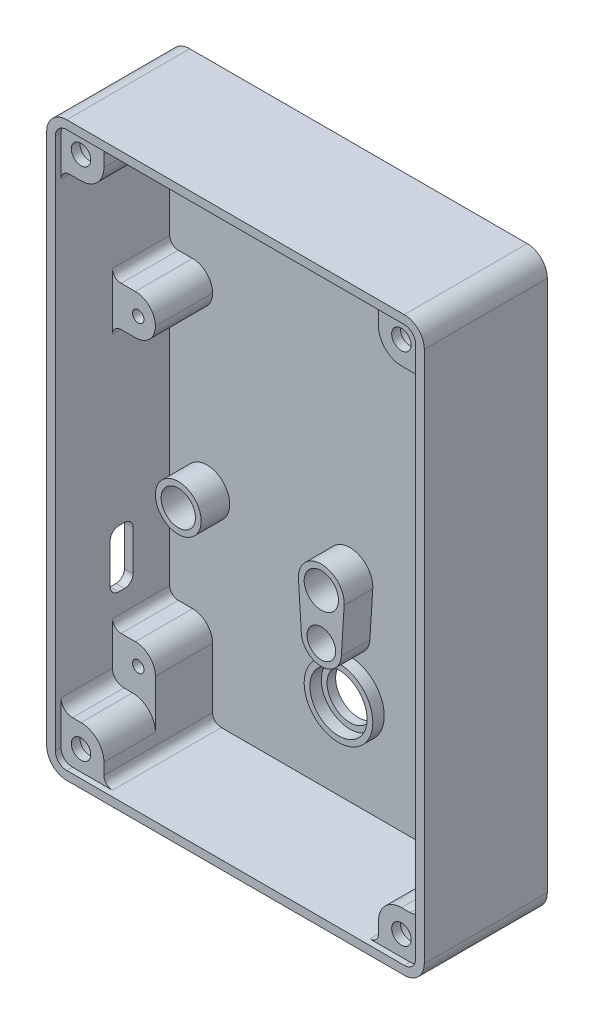
SolidWorks part; units mm, degrees
material "ABS"
ref_plane "Спереди" through (0, 0, 0) normal (0, 0, 1) x (1, 0, 0)
ref_plane "Сверху" through (0, 0, 0) normal (0, 1, 0) x (1, 0, 0)
ref_plane "Справа" through (0, 0, 0) normal (1, 0, 0) x (0, 0, -1)
sketch "Эскиз1" plane through (0, 0, 0) normal (0, 0, 1) x (1, 0, 0)
  line L1 (-33, -50) -> (33, -50)
  line L2 (-33, -50) -> (-33, 50)
  line L3 (-33, 50) -> (33, 50)
  line L4 (33, -50) -> (33, 50)
  line L5 (-33, -50) -> (33, 50) construction
  line L6 (-33, 50) -> (33, -50) construction
  line L7 (-31.5, -48.5) -> (31.5, -48.5)
  line L8 (-31.5, -48.5) -> (-31.5, 48.5)
  line L9 (-31.5, 48.5) -> (31.5, 48.5)
  line L10 (31.5, -48.5) -> (31.5, 48.5)
  line L11 (-31.5, -48.5) -> (31.5, 48.5) construction
  line L12 (-31.5, 48.5) -> (31.5, -48.5) construction
  point P0 (0, 0)
  point P6 (0, 0)
  dimension "D1" = 66
  dimension "D2" = 100
  dimension "D3" = 1.5
  dimension "D4" = 1.5
extrude "Бобышка-Вытянуть1" add sketch "Эскиз1" along normal blind 20
sketch "Эскиз3" plane through (0, 0, 0) normal (0, 0, -1) x (-1, 0, 0)
  line L1 (-33, 50) -> (33, 50)
  line L2 (-33, 50) -> (-33, -50)
  line L3 (-33, -50) -> (33, -50)
  line L4 (33, 50) -> (33, -50)
extrude "Бобышка-Вытянуть2" add sketch "Эскиз3" along normal blind 1.5
sketch "Эскиз4" plane through (0, 0, 0) normal (0, 0, 1) x (1, 0, 0)
  line L0 (-31.5, 48.5) -> (-31.5, -48.5) construction
  line L1 (-31.5, 20) -> (-24, 20)
  line L2 (-31.5, 20) -> (-31.5, 13)
  line L3 (-31.5, 13) -> (-24, 13)
  line L4 (-24, 20) -> (-24, 13)
  line L5 (31.5, -48.5) -> (31.5, 48.5) construction
  line L6 (31.5, 20) -> (24, 20)
  line L7 (31.5, 20) -> (31.5, 13)
  line L8 (31.5, 13) -> (24, 13)
  line L9 (24, 20) -> (24, 13)
  line L10 (-31.5, -48.5) -> (31.5, -48.5) construction
  line L11 (-31.5, -41) -> (-24, -41)
  line L12 (-31.5, -41) -> (-31.5, -33)
  line L13 (-31.5, -33) -> (-24, -33)
  line L14 (-24, -41) -> (-24, -33)
  line L15 (31.5, -41) -> (24, -41)
  line L16 (31.5, -41) -> (31.5, -33)
  line L17 (31.5, -33) -> (24, -33)
  line L18 (24, -41) -> (24, -33)
  line L19 (31.5, -48.5) -> (31.5, 48.5) construction
  dimension "D1" = 7.5
  dimension "D2" = 8
  dimension "D3" = 7
  dimension "D4" = 46
  dimension "D5" = 7.5
extrude "Бобышка-Вытянуть3" add sketch "Эскиз4" along normal blind 10
sketch "Эскиз5" plane through (0, 0, 10) normal (0, 0, 1) x (1, 0, 0)
  line L1 (-24, -41) -> (-24, -33) construction
  line L2 (-24, 13) -> (-24, 20) construction
  circle A0 centre (-27, 16.5) radius 1
  circle A1 centre (27, 16.5) radius 1
  circle A2 centre (-27, -36.5) radius 1
  circle A3 centre (27, -36.5) radius 1
  point P10 (-24, 16.5)
  point P13 (-27, -36.5)
  dimension "D5" = 2
  dimension "D6" = 53
  dimension "D1" = 54
  dimension "D2" = 3
sketch "Эскиз8" plane through (0, 0, 0) normal (0, 0, 1) x (1, 0, 0)
  line L0 (-24, -41) -> (-24, -33) construction
  line L1 (-31.5, 48.5) -> (-24, 48.5)
  line L2 (-31.5, 48.5) -> (-31.5, 41)
  line L3 (-31.5, 41) -> (-24, 41)
  line L4 (-24, 48.5) -> (-24, 41)
  line L5 (31.5, 48.5) -> (24, 48.5)
  line L6 (31.5, 48.5) -> (31.5, 41)
  line L7 (31.5, 41) -> (24, 41)
  line L8 (24, 48.5) -> (24, 41)
  line L9 (31.5, -48.5) -> (24, -48.5)
  line L10 (31.5, -48.5) -> (31.5, -41)
  line L11 (31.5, -41) -> (24, -41)
  line L12 (24, -48.5) -> (24, -41)
  line L13 (-31.5, -48.5) -> (-24, -48.5)
  line L14 (-31.5, -48.5) -> (-31.5, -41)
  line L15 (-31.5, -41) -> (-24, -41)
  line L16 (-24, -48.5) -> (-24, -41)
  line L18 (24, -33) -> (24, -41) construction
  line L19 (-24, 20) -> (-31.5, 20) construction
  line L21 (-31.5, -41) -> (-24, -41) construction
extrude "Бобышка-Вытянуть4" add sketch "Эскиз8" along normal blind 19
fillet "Скругление1" radius 1.5 12 edges at (-31.5, -33, 5) (-24, -48.5, 9.5) (24, -48.5, 9.5) (31.5, -33, 5) (31.5, 13, 5) (31.5, 20, 5) (-31.5, 13, 5) (-31.5, 20, 5) (-31.5, 41, 9.5) (-24, 48.5, 9.5) (31.5, 41, 9.5) (24, 48.5, 9.5)
fillet "Скругление3" radius 2 6 edges at (-31.5, -48.5, 19.5) (-31.5, -41, 14.5) (31.5, -48.5, 19.5) (31.5, -41, 14.5) (-31.5, 48.5, 19.5) (31.5, 48.5, 19.5)
fillet "Скругление4" radius 3.5 4 edges at (-33, -50, 9.25) (33, -50, 9.25) (33, 50, 9.25) (-33, 50, 9.25)
sketch "Эскиз9" plane through (0, 0, 0) normal (0, 0, 1) x (1, 0, 0)
  circle A0 centre (-25, -14) radius 3
  circle A1 centre (25, -14) radius 3
  circle A2 centre (0, -22) radius 2.5
  circle A3 centre (0, -14) radius 3
  circle A4 centre (0, -32.5) radius 4
  dimension "D1" = 6
  dimension "D6" = 8
  dimension "D8" = 5
  dimension "D2" = 8
  dimension "D3" = 10.5
  dimension "D4" = 25
  dimension "D5" = 25
  dimension "D7" = 4
extrude "Вырез-Вытянуть1" cut sketch "Эскиз9" against normal through all
sketch "Эскиз10" plane through (0, 0, 0) normal (0, 0, 1) x (1, 0, 0)
  line L0 (3.9922, -14.25) -> (3.4932, -22.2188)
  line L1 (-3.9922, -14.25) -> (-3.4932, -22.2188)
  circle A0 centre (-25, -14) radius 3
  circle A1 centre (0, -22) radius 2.5 construction
  circle A2 centre (0, -14) radius 3
  circle A3 centre (25, -14) radius 3
  circle A4 centre (0, -22) radius 2.5
  circle A5 centre (-25, -14) radius 3 construction
  circle A6 centre (0, -14) radius 4
  circle A7 centre (25, -14) radius 4
  circle A9 centre (-25, -14) radius 4
  arc A12 (-3.4932, -22.2188) -> (3.4932, -22.2188) centre (0, -22) ccw
  circle M1 centre (-25, -14) radius 3
  circle M2 centre (0, -14) radius 3
  circle M3 centre (0, -22) radius 2.5
  circle M4 centre (25, -14) radius 3
  dimension "D1" = 1
  dimension "D2" = 1
extrude "Бобышка-Вытянуть5" add sketch "Эскиз10" along normal blind 5 contours L1 A12 L0 A6 M3 | A6 M2 | A7 M4 | A9 M1 region at (3.605, -18.2258, 0) region at (0, -17.8869, 0) region at (21.1131, -14, 0) region at (-28.8869, -14, 0)
sketch "Эскиз11" plane through (0, 0, -1.5) normal (0, 0, -1) x (-1, 0, 0)
  line L0 (29.5, 50) -> (-29.5, 50) construction
  line L1 (33, -46.5) -> (33, 46.5) construction
  line L2 (-29.5, -50) -> (29.5, -50) construction
  line L3 (-33, 46.5) -> (-33, -46.5) construction
  circle A0 centre (-28, 45) radius 3
  circle A1 centre (28, 45) radius 3
  circle A2 centre (28, -45) radius 3
  circle A3 centre (-28, -45) radius 3
  dimension "D2" = 6
  dimension "D1" = 5
  dimension "D3" = 5
  dimension "D4" = 5
  dimension "D5" = 5
extrude "Вырез-Вытянуть2" cut sketch "Эскиз11" against normal blind 19
sketch "Эскиз12" plane through (0, 0, 17.5) normal (0, 0, -1) x (-1, 0, 0)
  point P0 (-28, 45)
  point P1 (28, 45)
  point P3 (28, -45)
  point P5 (-28, -45)
hole_wizard "Отверстие с зазором M31" positions "Эскиз13" profile "Эскиз14" hole size "M3" standard "DIN" end condition through all
sketch "Эскиз13" plane through (0, 0, 17.5) normal (0, 0, -1) x (-1, 0, 0)
  point P0 (-28, 45)
  point P3 (28, 45)
  point P6 (28, -45)
  point P9 (-28, -45)
sketch "Эскиз14" plane through (28, 45, 17.5) normal (1, 0, 0) x (0, 1, 0)
  line L0 (0, 0) -> (0, 2.5)
  line L1 (0, 2.5) -> (1.7, 2.5)
  line L2 (1.7, 2.5) -> (1.7, 0)
  line L5 (1.7, 0) -> (0, 0)
  line L11 (0, -6.35) -> (0, 107.95) construction
  dimension "Диаметр сквозного отверстия" = 3.4
  dimension "Глубина сквозного отверстия" = 2.5
extrude "Вырез-Вытянуть4" cut sketch "Эскиз5" against normal blind 4
sketch "Эскиз15" plane through (-31.5, 0, 0) normal (-1, 0, 0) x (0, 0, 1)
  line L1 (6.4, -28) -> (10.4, -28)
  line L2 (6.4, -28) -> (6.4, -18)
  line L3 (6.4, -18) -> (10.4, -18)
  line L4 (10.4, -28) -> (10.4, -18)
  line L5 (10, -39) -> (10, -31.5) construction
  dimension "D1" = 4
  dimension "D2" = 10
  dimension "D3" = 8.5
  dimension "D4" = 0.4
extrude "Вырез-Вытянуть3" cut sketch "Эскиз15" along normal up to surface (1.5 mm away) up to face at (-33, 0, 9.25)
fillet "Скругление5" radius 1.5 4 edges at (-32.25, -28, 10.4) (-32.25, -18, 10.4) (-32.25, -18, 6.4) (-32.25, -28, 6.4)
sketch "Эскиз16" plane through (0, 0, 0) normal (0, 0, 1) x (1, 0, 0)
  circle A0 centre (0, -32.5) radius 5
  circle A1 centre (0, -32.5) radius 6
  dimension "D1" = 1
  dimension "D2" = 10
extrude "Бобышка-Вытянуть6" add sketch "Эскиз16" along normal blind 2
fillet "Скругление6" radius 3.5 6 edges at (24, -33, 5) (-24, -33, 5) (24, 13, 5) (24, 20, 5) (-24, 13, 5) (-24, 20, 5)
fillet "Скругление7" radius 4 4 edges at (24, 41, 9.5) (-24, -41, 14.5) (24, -41, 14.5) (-24, 41, 9.5)
